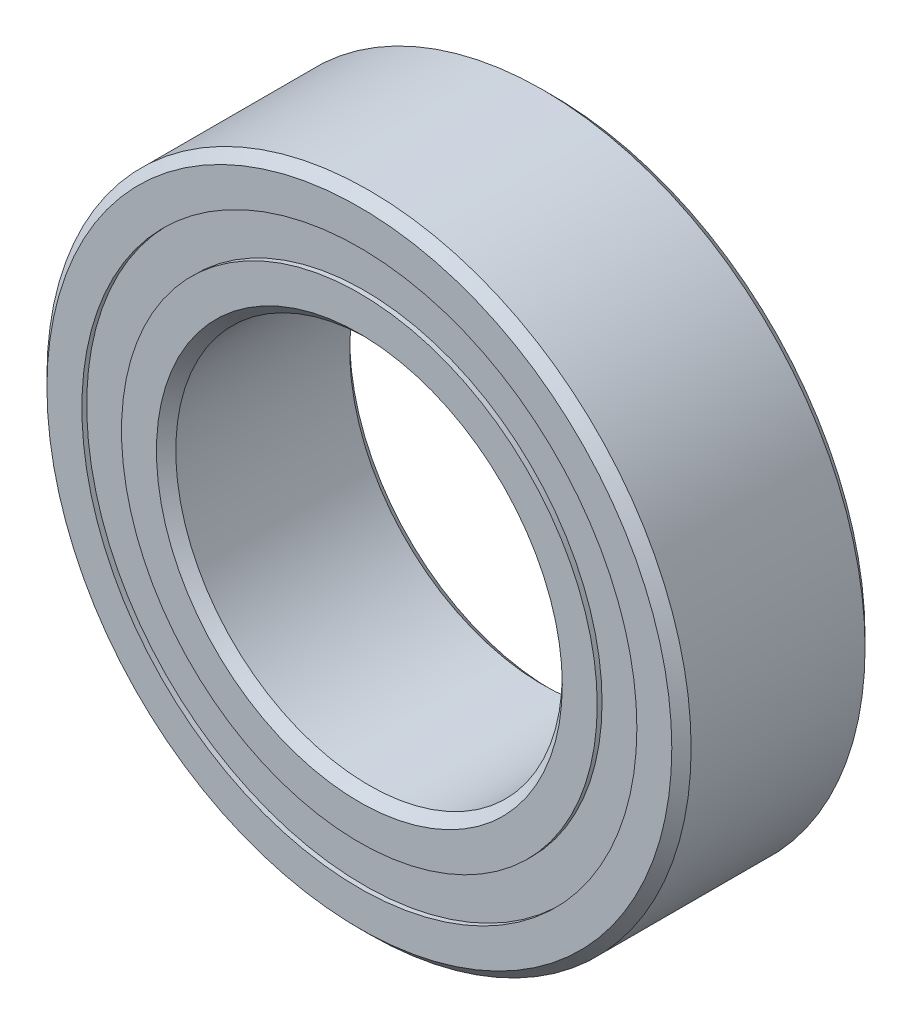
SolidWorks part; units mm, degrees
ref_plane "Front Plane" through (0, 0, 0) normal (0, 0, 1) x (1, 0, 0)
ref_plane "Top Plane" through (0, 0, 0) normal (0, 1, 0) x (1, 0, 0)
ref_plane "Right Plane" through (0, 0, 0) normal (1, 0, 0) x (0, 0, -1)
sketch "Sketch1" plane through (0, 0, 0) normal (1, 0, 0) x (0, 0, -1)
  line L0 (-1.5, 0) -> (1.5, 0) construction
  line L1 (0, 5) -> (0, -5) construction
  line L2 (1.35, 5) -> (-1.35, 5)
  line L3 (-1.35, 5) -> (-1.5, 4.85)
  line L4 (-1.5, 4.85) -> (-1.5, 4.3077)
  line L5 (-1.5, 4.3077) -> (-0.6667, 4.3077)
  line L6 (1.5, 4.3077) -> (0.6667, 4.3077)
  line L7 (1.5, 4.85) -> (1.5, 4.3077)
  line L8 (1.35, 5) -> (1.5, 4.85)
  line L9 (0, 5) -> (0, 4) construction
  line L10 (0, 4) -> (0, 3) construction
  arc A0 (-0.6667, 4.3077) -> (0.6667, 4.3077) centre (0, 4) cw
  point P14 (0, 3)
  dimension "D3" = 1.3333
  dimension "D1" = 45
  dimension "Width" = 3
  dimension "OD" = 10
  dimension "D2" = 0.15
  dimension "Shaft Dia" = 6
  dimension "D4" = 0.3077
revolve "Revolve1" add sketch "Sketch1" angle 360 about L0
sketch "Sketch3" plane through (0, 0, 0) normal (1, 0, 0) x (0, 0, -1)
  line L0 (-1.5, 3.6923) -> (-0.6667, 3.6923)
  line L1 (0, 5) -> (0, -5) construction
  line L2 (-1.5, 4.85) -> (-1.5, 4.3077) construction
  line L3 (-1.5, 3.6923) -> (-1.5, 3.15)
  line L4 (-1.35, 5) -> (-1.5, 4.85) construction
  line L5 (-1.5, 3.15) -> (-1.35, 3)
  line L6 (-1.35, 3) -> (1.35, 3)
  line L7 (1.35, 5) -> (1.35, -5) construction
  line L8 (1.35, 3) -> (1.5, 3.15)
  line L9 (1.5, -4.85) -> (1.5, 4.85) construction
  line L10 (1.5, 3.15) -> (1.5, 3.6923)
  line L11 (1.5, 3.6923) -> (0.6667, 3.6923)
  line L13 (1.35, 5) -> (1.5, 4.85) construction
  arc A0 (0.6667, 4.3077) -> (-0.6667, 4.3077) centre (0, 4) ccw construction
  arc A1 (0.6667, 3.6923) -> (-0.6667, 3.6923) centre (0, 4) cw
revolve "Revolve3" add sketch "Sketch3" angle 360 about L0
sketch "Sketch4" plane through (0, 0, 0) normal (1, 0, 0) x (0, 0, -1)
  line L0 (-0.7342, 4) -> (0.7342, 4)
  arc A2 (-0.7342, 4) -> (0.7342, 4) centre (0, 4) cw
  arc A3 (0.6667, 4.3077) -> (-0.6667, 4.3077) centre (0, 4) ccw construction
revolve "Revolve4" add sketch "Sketch4" angle 360 about L0
ref_axis "Axis1" through (0, 0, -1.5) along (0, 0, 1)
pattern_circular "CirPattern1" count 12 every 30 about axis through (0, 0, -1.5) along (0, 0, 1) of bodies 104
sketch "Sketch5" plane through (0, 0, 0) normal (1, 0, 0) x (0, 0, -1)
  line L0 (-1.5, 4.3077) -> (-0.6667, 4.3077) construction
  line L1 (-1.425, 4.3077) -> (-0.7342, 4.3077)
  line L2 (-1.425, 4.3077) -> (-1.425, 3.6923)
  line L3 (-1.425, 3.6923) -> (-0.7342, 3.6923)
  line L4 (-0.7342, 4.3077) -> (-0.7342, 3.6923)
  line L5 (-1.5, 3.6923) -> (-0.6667, 3.6923) construction
  line L6 (1.5, 4.3077) -> (0.6667, 4.3077) construction
  line L7 (1.425, 4.3077) -> (0.7342, 4.3077)
  line L8 (1.425, 4.3077) -> (1.425, 3.6923)
  line L9 (1.425, 3.6923) -> (0.7342, 3.6923)
  line L10 (0.7342, 4.3077) -> (0.7342, 3.6923)
  line L11 (1.5, 3.6923) -> (0.6667, 3.6923) construction
  line L12 (-1.35, 5) -> (-1.5, 4.85) construction
  point P18 (-1.425, 4.925)
revolve "Revolve5" add sketch "Sketch5" angle 360 about L0
sketch "Sketch6" plane through (0, 0, 0) normal (1, 0, 0) x (0, 0, -1)
  line L0 (1.5, 0) -> (-1.5, 0) construction
  line L1 (1.5, 4.3077) -> (0.4, 4.3077)
  line L2 (1.5, 4.3077) -> (1.5, 9.5)
  line L3 (1.5, 9.5) -> (0.4, 9.5)
  line L4 (0.4, 4.3077) -> (0.4, 9.5)
  dimension "Th" = 1.1
  dimension "Flange OD" = 19
revolve "Revolve6" [suppressed] add sketch "Sketch6" angle 360 about L0
equation "\"D2@Sketch1\" = \"Width@Sketch1\"*.05"
equation "\"D3@Sketch1\" = \"Width@Sketch1\"/2.25"
equation "\"D4@Sketch1\" = (((\"OD@Sketch1\"-\"Width@Sketch1\")/2)/3.25)/3.5"
equation "\"D2@CirPattern1\" = 360/\"Balls@CirPattern1\""
